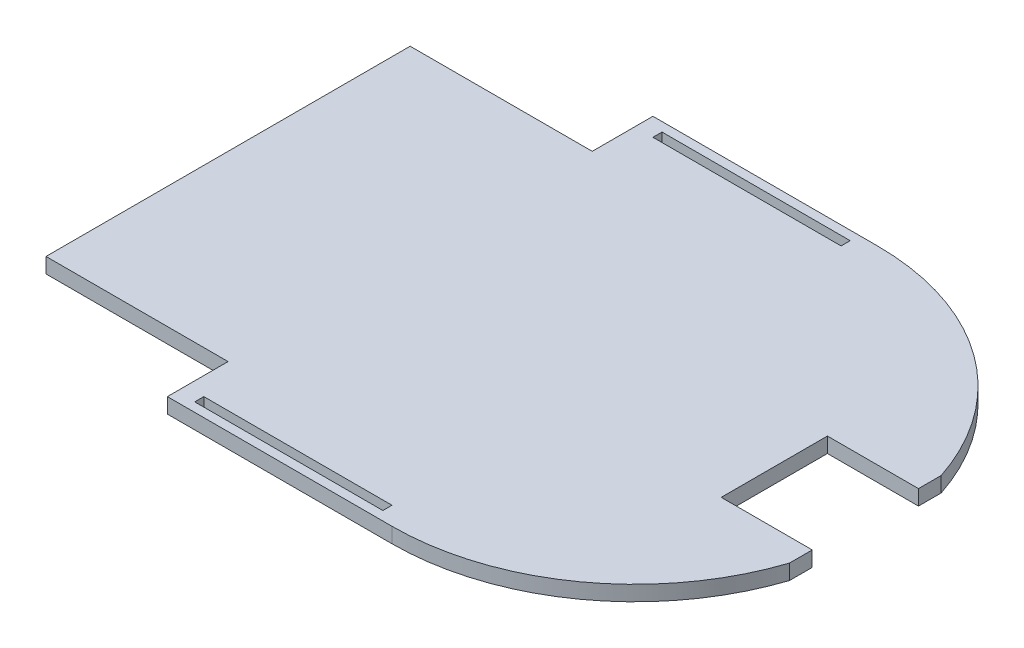
SolidWorks part; units mm, degrees
ref_plane "Piano frontale" through (0, 0, 0) normal (0, 0, 1) x (1, 0, 0)
ref_plane "Piano superiore" through (0, 0, 0) normal (0, 1, 0) x (1, 0, 0)
ref_plane "Piano destro" through (0, 0, 0) normal (1, 0, 0) x (0, 0, -1)
sketch "Schizzo1" plane through (0, 0, 0) normal (0, 1, 0) x (1, 0, 0)
  line L0 (60, 60) -> (60, 80)
  line L1 (0, 60) -> (60, 60)
  line L2 (0, 60) -> (0, -60)
  line L3 (0, -60) -> (60, -60)
  line L4 (60, 60) -> (60, -60) construction
  line L5 (60, 80) -> (134.0066, 80)
  line L6 (210, 25) -> (210, -25)
  line L7 (134.0066, -80) -> (60, -80)
  line L8 (60, -80) -> (60, -60)
  line L9 (210, 0) -> (60, 0) construction
  arc A0 (210, 25) -> (134.0066, 80) centre (134.0066, 0) ccw
  arc A1 (134.0066, -80) -> (210, -25) centre (134.0066, 0) ccw
  dimension "D5" = 50
  dimension "D6" = 80
  dimension "D1" = 120
  dimension "D2" = 60
  dimension "D3" = 150
  dimension "D4" = 20
extrude "Estrusione-Estrusione1" add sketch "Schizzo1" along normal blind 5
sketch "Schizzo2" plane through (0, 5, 0) normal (0, 1, 0) x (1, 0, 0)
  line L0 (210, 17.5) -> (180, 17.5)
  line L1 (210, -25) -> (210, 25) construction
  line L2 (180, 17.5) -> (180, -17.5)
  line L3 (180, -17.5) -> (210, -17.5)
  line L4 (180, 0) -> (210, 0) construction
  line L5 (210, -25) -> (210, -17.5) construction
  line L6 (210, 25) -> (210, 17.5) construction
  dimension "D1" = 30
  dimension "D2" = 35
extrude "Taglio-Estrusione1" cut sketch "Schizzo2" against normal through all and the other way through all
sketch "Schizzo4" plane through (0, 5, 0) normal (0, 1, 0) x (1, 0, 0)
  line L0 (97.0033, -80) -> (97.0033, -77) construction
  line L1 (66, -77) -> (128.0066, -77)
  line L2 (66, -77) -> (66, -74)
  line L3 (66, -74) -> (128.0066, -74)
  line L4 (128.0066, -77) -> (128.0066, -74)
  line L9 (66, 77) -> (128.0066, 77)
  line L10 (66, 77) -> (66, 74)
  line L11 (66, 74) -> (128.0066, 74)
  line L12 (128.0066, 77) -> (128.0066, 74)
  line L13 (60, -80) -> (134.0066, -80) construction
  line L14 (66, -75.5) -> (60, -75.5) construction
  line L15 (60, -60) -> (60, -80) construction
  line L16 (97.0033, 80) -> (97.0033, 77) construction
  line L17 (134.0066, 80) -> (60, 80) construction
  line L18 (66, 75.5) -> (60, 75.5) construction
  line L19 (60, 80) -> (60, 60) construction
  dimension "D1" = 3
  dimension "D2" = 3
  dimension "D3" = 6
extrude "Taglio-Estrusione2" cut sketch "Schizzo4" against normal blind 10
